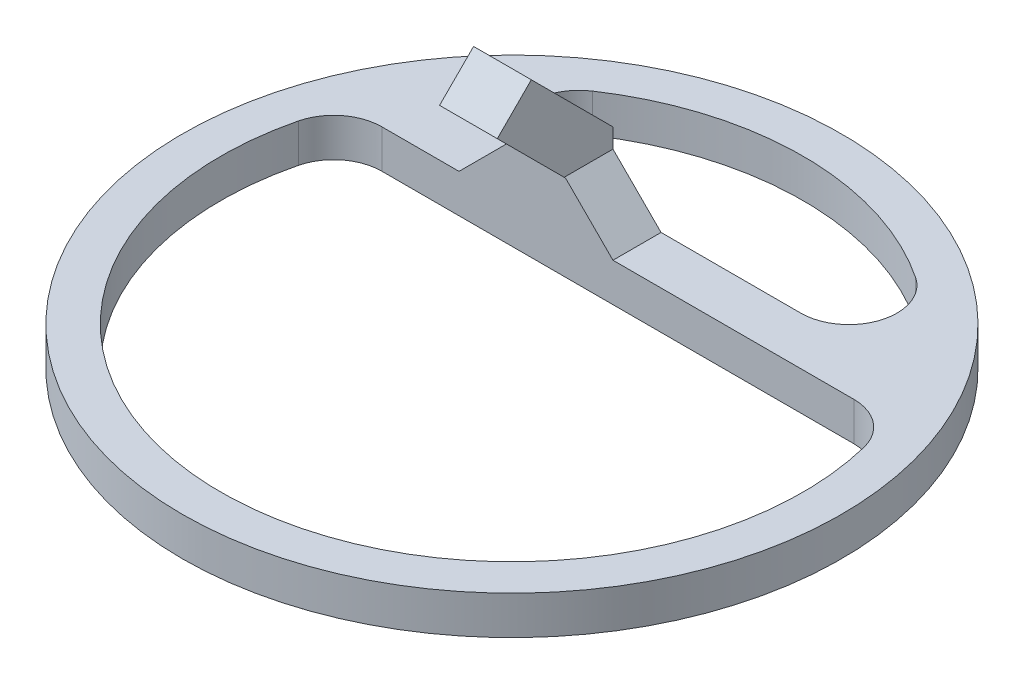
SolidWorks part; units mm, degrees
ref_plane "Front Plane" through (0, 0, 0) normal (0, 0, 1) x (1, 0, 0)
ref_plane "Top Plane" through (0, 0, 0) normal (0, 1, 0) x (1, 0, 0)
ref_plane "Right Plane" through (0, 0, 0) normal (1, 0, 0) x (0, 0, -1)
sketch "Sketch1" plane through (0, 0, 0) normal (0, 1, 0) x (1, 0, 0)
  circle A0 centre (0, 0) radius 34.25
  circle A1 centre (0, 0) radius 30.25
  dimension "D1" = 68.5
  dimension "D2" = 4
extrude "Boss-Extrude1" add sketch "Sketch1" along normal blind 4
sketch "Sketch2" plane through (0, 0, 0) normal (1, 0, 0) x (0, 0, -1)
  line L0 (3.9792, 15.9497) -> (11, 8.9289)
  line L1 (11, 8.9289) -> (11, 4)
  line L2 (30.25, 4) -> (-30.25, 4) construction
  line L3 (11, 4) -> (16, 4)
  line L4 (16, 4) -> (16, 11)
  line L5 (16, 11) -> (7.5147, 19.4853)
  line L6 (7.5147, 19.4853) -> (3.9792, 15.9497)
  dimension "D1" = 135
  dimension "D2" = 5
  dimension "D3" = 5
  dimension "D4" = 12
  dimension "D5" = 7
  dimension "D6" = 11
extrude "Boss-Extrude2" add sketch "Sketch2" along normal blind 6 from offset 11.5 separate body offset against normal yes
sketch "Sketch5" plane through (0, 4, 0) normal (0, -1, 0) x (1, 0, 0)
  line L0 (28.1791, -11) -> (-28.1791, -11)
  line L1 (25.6722, -16) -> (-25.6722, -16)
  line L2 (-5.5, -11) -> (-11.5, -11) construction
  line L3 (-5.5, -16) -> (-11.5, -16) construction
  circle A0 centre (0, 0) radius 30.25 construction
  arc A1 (-28.1791, -11) -> (-25.6722, -16) centre (0, 0) ccw
  arc A2 (28.1791, -11) -> (25.6722, -16) centre (0, 0) cw
extrude "Boss-Extrude3" add sketch "Sketch5" along normal up to surface (4 mm away) up to face at (0, 0, 34.25)
chamfer "Chamfer1" distance 5 angle 45 2 edges at (-11.5, 4, -13.5) (-5.5, 4, -13.5)
fillet "Fillet1" radius 5 4 edges at (25.6722, 2, -16) (28.1791, 2, -11) (-25.6722, 2, -16) (-28.1791, 2, -11)
sketch "Sketch6" plane through (0, 9.9645, -9.9645) normal (0, -0.7071, 0.7071) x (1, 0, 0)
  line L0 (-8.5, -1.4645) -> (-8.5, 4.5355) construction
  line L1 (-5.4289, -1.4645) -> (-11.5711, -1.4645) construction
  circle A0 centre (-8.5, 4.5355) radius 1.65
  dimension "D2" = 3.3
  dimension "D1" = 6
extrude "Cut-Extrude2" cut sketch "Sketch6" against normal up to next
